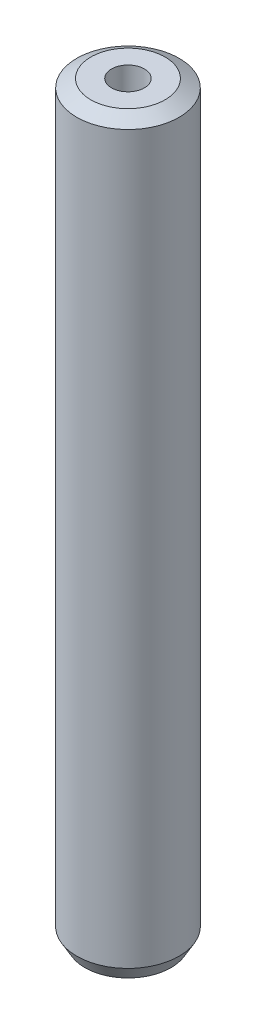
SolidWorks part; units mm, degrees
ref_plane "Front Plane" through (0, 0, 0) normal (0, 0, 1) x (1, 0, 0)
ref_plane "Top Plane" through (0, 0, 0) normal (0, 1, 0) x (1, 0, 0)
ref_plane "Right Plane" through (0, 0, 0) normal (1, 0, 0) x (0, 0, -1)
sketch "Sketch1" plane through (0, 0, 0) normal (0, 1, 0) x (1, 0, 0)
  circle A0 centre (0, 0) radius 25
  dimension "SHAFT_OD" = 50
extrude "Boss-Extrude1" add sketch "Sketch1" along normal blind 365.8035
sketch "Sketch2" plane through (0, 0, 0) normal (0, 1, 0) x (1, 0, 0)
  circle A0 centre (0, 0) radius 8.0374
  dimension "BORE_D" = 16.0748
extrude "Cut-Extrude1" cut sketch "Sketch2" along normal through all
chamfer "Chamfer1" distance 3.9637 angle 60 2 edges at (0, 365.8035, 25) (0, 0, 25) first distance on face at (0, 365.8035, 25) first distance on face at (0, 0, 8.0374)
